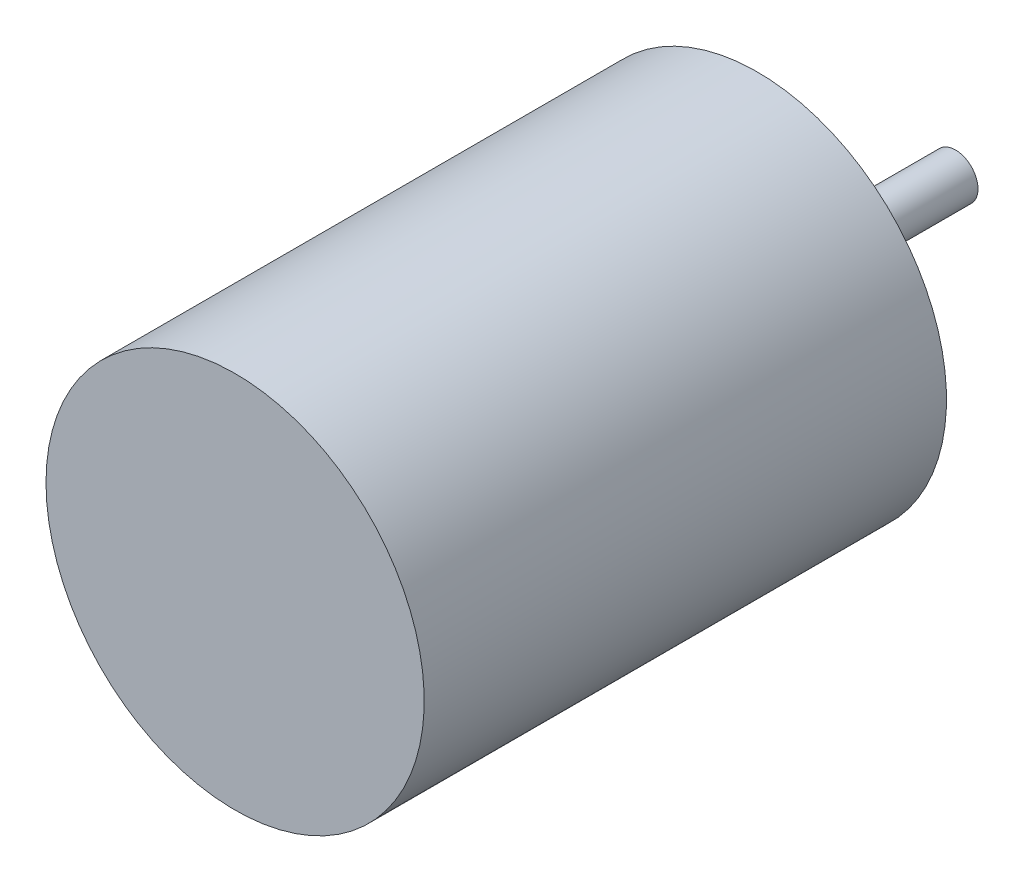
SolidWorks part; units mm, degrees
ref_plane "Front Plane" through (0, 0, 0) normal (0, 0, 1) x (1, 0, 0)
ref_plane "Top Plane" through (0, 0, 0) normal (0, 1, 0) x (1, 0, 0)
ref_plane "Right Plane" through (0, 0, 0) normal (1, 0, 0) x (0, 0, -1)
sketch "Sketch1" plane through (0, 0, 0) normal (0, 0, 1) x (1, 0, 0)
  circle A0 centre (75.771, -68.5827) radius 21
extrude "Мотор" add sketch "Sketch1" along normal blind 58
sketch "Sketch2" plane through (0, 0, 0) normal (0, 0, -1) x (-1, 0, 0)
  circle A0 centre (-75.771, -68.5827) radius 2.5
extrude "Вал" add sketch "Sketch2" along normal blind 22
ref_axis "Ось вала" through (75.771, -68.5827, -22) along (0, 0, 1)
